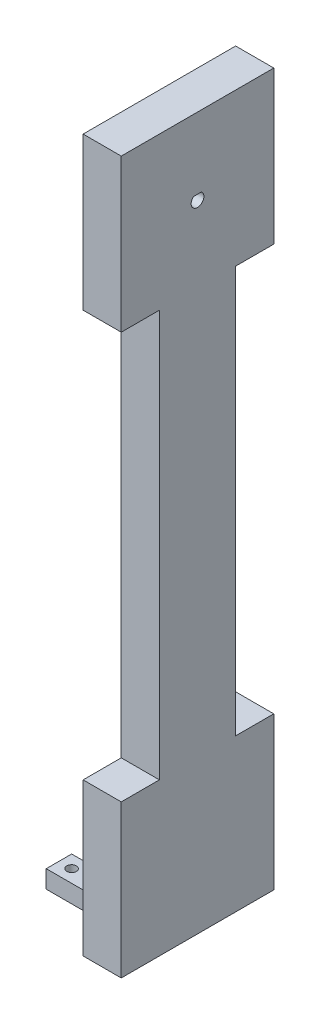
SolidWorks part; units mm, degrees
ref_plane "Front Plane" through (0, 0, 0) normal (0, 0, 1) x (1, 0, 0)
ref_plane "Top Plane" through (0, 0, 0) normal (0, 1, 0) x (1, 0, 0)
ref_plane "Right Plane" through (0, 0, 0) normal (1, 0, 0) x (0, 0, -1)
sketch "Sketch1" plane through (0, 0, 0) normal (1, 0, 0) x (0, 0, -1)
  line L1 (30, -30) -> (-30, -30)
  line L2 (30, -30) -> (30, 30)
  line L3 (30, 30) -> (-30, 30)
  line L4 (-30, -30) -> (-30, 30)
  line L5 (30, -30) -> (-30, 30) construction
  line L6 (30, 30) -> (-30, -30) construction
  point P0 (0, 0)
  dimension "D1" = 60
  dimension "D2" = 60
extrude "Boss-Extrude1" add sketch "Sketch1" along normal blind 15
sketch "Sketch2" plane through (15, 0, 0) normal (1, 0, 0) x (0, 0, -1)
  line L0 (0, 0) -> (0, 30) construction
  line L1 (30, 30) -> (-30, 30) construction
  line L2 (1.5, 2) -> (-1.5, 2)
  circle A0 centre (0, 0) radius 2.5
  dimension "D1" = 5
  dimension "D2" = 3
extrude "Cut-Extrude1" cut sketch "Sketch2" against normal up to surface (15 mm away) contours A0 region at (15, -0.1209, 0) up to face at (0, 0, 0)
sketch "Sketch8" plane through (0, -30, 0) normal (0, -1, 0) x (1, 0, 0)
  line L0 (0, 30) -> (0, 15) construction
  line L1 (0, 30) -> (0, -30) construction
  line L2 (15, 30) -> (15, -30) construction
  line L3 (0, 15) -> (15, 15)
  line L4 (0, 15) -> (0, -15)
  line L5 (0, -15) -> (15, -15)
  line L6 (15, 15) -> (15, -15)
  line L7 (0, -15) -> (0, -30) construction
  dimension "D1" = 30
extrude "Boss-Extrude2" add sketch "Sketch8" along normal blind 160
sketch "Sketch9" plane through (0, -190, 0) normal (0, -1, 0) x (1, 0, 0)
  line L0 (0, 0) -> (0, 30)
  line L1 (0, 15) -> (0, -15) construction
  line L2 (15, 30) -> (15, -30)
  line L3 (15, -30) -> (0, -30)
  line L4 (15, 30) -> (0, 30)
  line L5 (0, -30) -> (0, 0)
  dimension "D1" = 60
extrude "Boss-Extrude3" add sketch "Sketch9" along normal blind 60
sketch "Sketch10" plane through (0, 0, 0) normal (-1, 0, 0) x (0, 0, 1)
  line L0 (30, -250) -> (30, -240) construction
  line L1 (30, -250) -> (30, -190) construction
  line L2 (30, -240) -> (24.5087, -240) construction
  line L3 (0, -250) -> (0, -194.4433) construction
  line L4 (24.5087, -240) -> (14.5087, -240)
  line L5 (24.5087, -240) -> (24.5087, -233)
  line L6 (24.5087, -233) -> (14.5087, -233)
  line L7 (14.5087, -240) -> (14.5087, -233)
  line L8 (30, -250) -> (-30, -250) construction
  line L9 (-14.5087, -240) -> (-14.5087, -233)
  line L10 (-24.5087, -233) -> (-14.5087, -233)
  line L11 (-24.5087, -240) -> (-24.5087, -233)
  line L12 (-24.5087, -240) -> (-14.5087, -240)
  dimension "D1" = 10
  dimension "D2" = 7
  dimension "D3" = 10
extrude "Boss-Extrude4" add sketch "Sketch10" along normal blind 20
sketch "Sketch12" plane through (0, -240, 0) normal (0, -1, 0) x (1, 0, 0)
  line L0 (-20, 24.5087) -> (-20, 19.5087) construction
  line L1 (-20, 14.5087) -> (-20, 24.5087) construction
  line L2 (-20, 19.5087) -> (-15.025, 19.5087) construction
  line L3 (-15.025, 19.5087) -> (-4.975, 19.5087) construction
  line L4 (-4.975, 19.5087) -> (0, 19.5087) construction
  line L5 (0, 14.5087) -> (0, 24.5087) construction
  line L6 (0, 19.5087) -> (0, -19.5087) construction
  line L7 (0, -24.5087) -> (0, -14.5087) construction
  line L8 (0, 0) -> (-23.535, 0) construction
  circle A0 centre (-15.025, 19.5087) radius 1.9
  circle A1 centre (-4.975, 19.5087) radius 1.9
  circle A2 centre (-4.975, -19.5087) radius 1.9
  circle A3 centre (-15.025, -19.5087) radius 1.9
  dimension "D2" = 3.8
  dimension "D1" = 10.05
extrude "Cut-Extrude2" cut sketch "Sketch12" against normal up to surface (7 mm away) up to face at (-10, -233, 19.5087)
